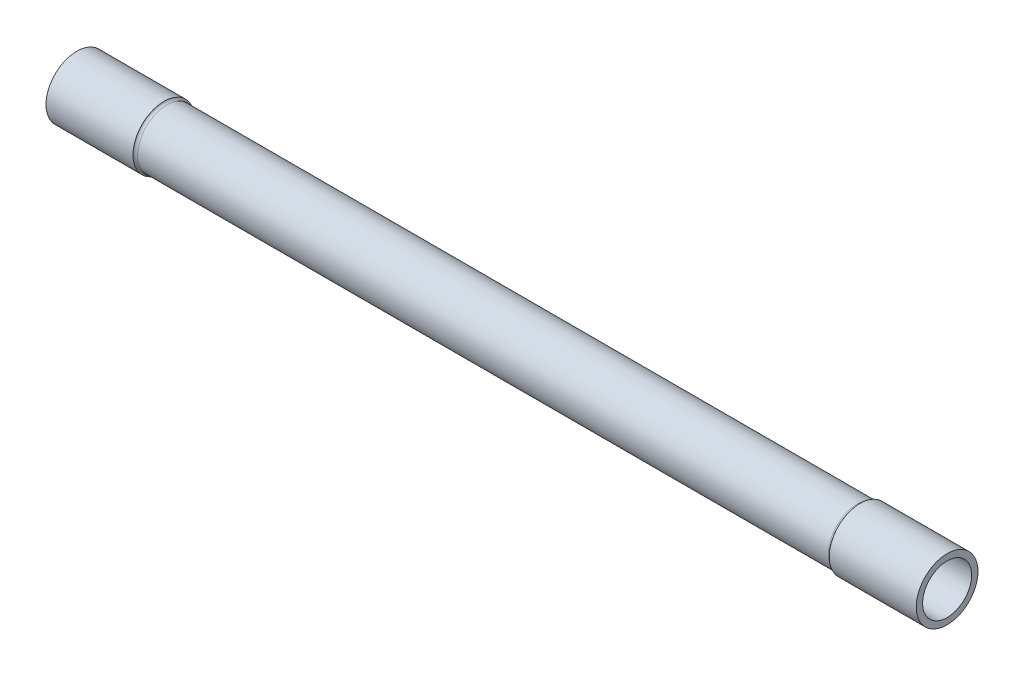
SolidWorks part; units mm, degrees
ref_plane "Front Plane" through (0, 0, 0) normal (0, 0, 1) x (1, 0, 0)
ref_plane "Top Plane" through (0, 0, 0) normal (0, 1, 0) x (1, 0, 0)
ref_plane "Right Plane" through (0, 0, 0) normal (1, 0, 0) x (0, 0, -1)
sketch "Sketch2" plane through (0, 0, 0) normal (1, 0, 0) x (0, 0, -1)
  circle A0 centre (0, 0) radius 25.4
  circle A1 centre (0, 0) radius 21.4884
  dimension "D1" = 50.8
  dimension "D2" = 3.9116
extrude "Boss-Extrude1" add sketch "Sketch2" along normal blind 762
sketch "Sketch3" plane through (762, 0, 0) normal (1, 0, 0) x (0, 0, -1)
  circle A0 centre (0, 0) radius 27.0256
  circle A1 centre (0, 0) radius 25.4
  circle M1 centre (0, 0) radius 25.4
  dimension "D1" = 54.0512
extrude "Boss-Extrude2" add sketch "Sketch3" against normal blind 76.2 contours A0 M1 region at (762, 0, 26.2612)
fillet "Fillet1" radius 2.54 1 edges at (685.8, 0, -25.4)
ref_plane "Plane1" through (381, 0, 0) normal (-1, 0, 0) x (0, 0, 1)
mirror "Mirror1" about plane through (381, 0, 0) normal (-1, 0, 0) of "Fillet1", "Boss-Extrude2"
